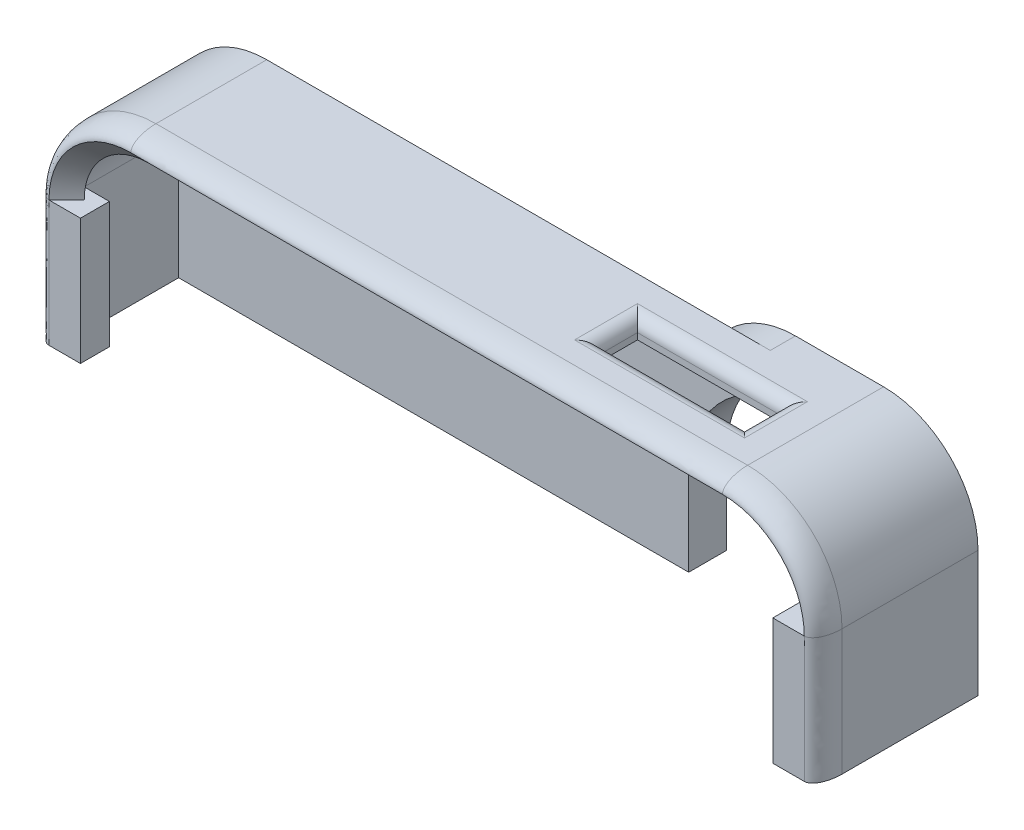
SolidWorks part; units mm, degrees
ref_plane "Front Plane" through (0, 0, 0) normal (0, 0, 1) x (1, 0, 0)
ref_plane "Top Plane" through (0, 0, 0) normal (0, 1, 0) x (1, 0, 0)
ref_plane "Right Plane" through (0, 0, 0) normal (1, 0, 0) x (0, 0, -1)
sketch "Sketch1" plane through (0, 0, 0) normal (0, 0, 1) x (1, 0, 0)
  line L0 (31, 17.5) -> (31, 0)
  line L1 (0, 0) -> (62, 0)
  line L2 (0, 0) -> (0, 10)
  line L3 (7.5, 17.5) -> (54.5, 17.5)
  line L4 (62, 0) -> (62, 10)
  line L5 (7.5, 16) -> (54.5, 16)
  line L9 (1.5, 0) -> (1.5, 10)
  line L12 (60.5, 10) -> (60.5, 0)
  arc A0 (0, 10) -> (7.5, 17.5) centre (7.5, 10) cw
  arc A1 (62, 10) -> (54.5, 17.5) centre (54.5, 10) ccw
  arc A2 (1.5, 10) -> (7.5, 16) centre (7.5, 10) cw
  arc A3 (60.5, 10) -> (54.5, 16) centre (54.5, 10) ccw
  dimension "D5" = 1.5
extrude "Boss-Extrude1" add sketch "Sketch1" along normal blind 10.8 contours L9 A2 L5 L0 L3 A0 L2 L1 | A3 L12 L1 L4 A1 L3 L0 L5 region at (42.75, 17.144, 0) region at (30.644, 16.75, 0)
sketch "Sketch2" plane through (0, 0, 0) normal (0, 0, -1) x (-1, 0, 0)
  line L0 (-1.5, 0) -> (-1.5, 10)
  line L1 (-7.5, 16) -> (-54.5, 16)
  line L2 (-60.5, 0) -> (-60.5, 10)
  line L3 (-60.5, 0) -> (-1.5, 0)
  arc A0 (-1.5, 10) -> (-7.5, 16) centre (-7.5, 10) ccw
  arc A1 (-54.5, 16) -> (-60.5, 10) centre (-54.5, 10) ccw
extrude "Boss-Extrude2" add sketch "Sketch2" against normal blind 1 separate body
combine bodies "Combine1" operation type add bodies to combine 102 101
sketch "Sketch3" plane through (0, 0, 10.8) normal (0, 0, 1) x (1, 0, 0)
  line L0 (0, 0) -> (3.5, 0)
  line L1 (0, 0) -> (0, 10)
  line L2 (0, 0) -> (0, 10) construction
  line L3 (3.5, 0) -> (3.5, 10)
  line L4 (3.5, 10) -> (0, 10)
  line L5 (1.5, 10) -> (1.5, 0)
  line L6 (31, 16) -> (31, -7.5027)
  line L7 (7.5, 16) -> (54.5, 16) construction
  line L8 (60.5, 10) -> (60.5, 0)
  line L9 (62, 0) -> (58.5, 0)
  line L10 (58.5, 10) -> (62, 10)
  line L11 (58.5, 0) -> (58.5, 10)
  line M7 (1.5, 0) -> (1.5, 10)
  line M11 (60.5, 10) -> (60.5, 0)
  dimension "D1" = 3.5
  dimension "D2" = 10
extrude "Boss-Extrude3" add sketch "Sketch3" against normal blind 2.3 contours L3 L4 L0 M7 | L11 L9 L10 M11 region at (2.5, 5, 10.8) region at (59.5, 5, 10.8)
fillet "Fillet1" radius 1 5 edges at (0, 5, 10.8) (62, 5, 10.8) (2.1967, 15.3033, 10.8) (59.8033, 15.3033, 10.8) (31, 17.5, 10.8) second distance 2 first distance on face at (31, 9.4708, 10.8)
sketch "Sketch4" plane through (0, 17.5, 0) normal (0, 1, 0) x (1, 0, 0)
  line L0 (62, -8.8) -> (62, 0) construction
  line L1 (51.5, -6.05) -> (40, -6.05)
  line L2 (51.5, -6.05) -> (51.5, -3.05)
  line L3 (51.5, -3.05) -> (40, -3.05)
  line L4 (40, -6.05) -> (40, -3.05)
  line L5 (7.5, 0) -> (54.5, 0) construction
  dimension "D1" = 10.5
  dimension "D2" = 11.5
  dimension "D3" = 3.05
  dimension "D4" = 3
extrude "Cut-Extrude1" cut sketch "Sketch4" against normal up to next
sketch "Sketch5" plane through (0, 0, 10.8) normal (0, 0, 1) x (1, 0, 0)
  line L1 (7.5, 15) -> (54.5, 15)
  line L2 (7.5, 16) -> (54.5, 16) construction
  line L4 (3.5, 10) -> (1.5, 10) construction
  line L5 (31, 16.5) -> (31, -2.3238) construction
  line L6 (54.5, 16.5) -> (7.5, 16.5) construction
  line L7 (59.5, 10) -> (60.5, 10)
  line L8 (54.5, 16) -> (7.5, 16)
  line L9 (1.5, 10) -> (2.5, 10)
  arc A1 (2.5, 10) -> (7.5, 15) centre (7.5, 10) cw
  arc A2 (59.5, 10) -> (54.5, 15) centre (54.5, 10) ccw
  arc A3 (60.5, 10) -> (54.5, 16) centre (54.5, 10) ccw
  arc A4 (7.5, 16) -> (1.5, 10) centre (7.5, 10) ccw
  dimension "D1" = 1
extrude "Boss-Extrude4" add sketch "Sketch5" against normal blind 2.3
chamfer "Chamfer1" distance 1.5 angle 45 3 edges at (58.0355, 13.5355, 10.8) (31, 15, 10.8) (3.9645, 13.5355, 10.8)
chamfer "Chamfer3" distance 1 angle 45 3 edges at (58.0355, 13.5355, 8.5) (31, 15, 8.5) (3.9645, 13.5355, 8.5)
sketch "Sketch6" plane through (0, 0, 0) normal (0, 0, -1) x (-1, 0, 0)
  line L0 (-59.98, 0) -> (-59.98, 6.7)
  line L1 (-59.98, 0) -> (-42.02, 0)
  line L2 (-42.02, 0) -> (-42.02, 6.7)
  arc A0 (-42.02, 6.7) -> (-59.98, 6.7) centre (-51, 6.7) ccw
extrude "Cut-Extrude2" cut sketch "Sketch6" against normal blind 2
sketch "Sketch9" plane through (0, 0, 0) normal (0, 0, -1) x (-1, 0, 0)
  line L0 (-62, 10) -> (-62, 0)
  line L1 (-62, 0) -> (-59.98, 0)
  line L2 (-59.98, 0) -> (-59.98, 6.7)
  line L3 (-42.02, 6.7) -> (-42.02, 0)
  line L4 (-42.02, 0) -> (-40, 0)
  line L5 (-42.02, 0) -> (0, 0) construction
  line L6 (-40, 0) -> (-40, 10)
  line L8 (-54.5, 17.5) -> (-47.5, 17.5)
  arc A0 (-59.98, 6.7) -> (-42.02, 6.7) centre (-51, 6.7) cw
  arc A1 (-47.5, 17.5) -> (-40, 10) centre (-47.5, 10) cw
  arc A2 (-54.5, 17.5) -> (-62, 10) centre (-54.5, 10) ccw
extrude "Boss-Extrude6" add sketch "Sketch9" along normal blind 2
fillet "Fillet2" radius 1 4 edges at (45.75, 17.5, 3.05) (51.5, 17.5, 4.55) (45.75, 17.5, 6.05) (40, 17.5, 4.55)
